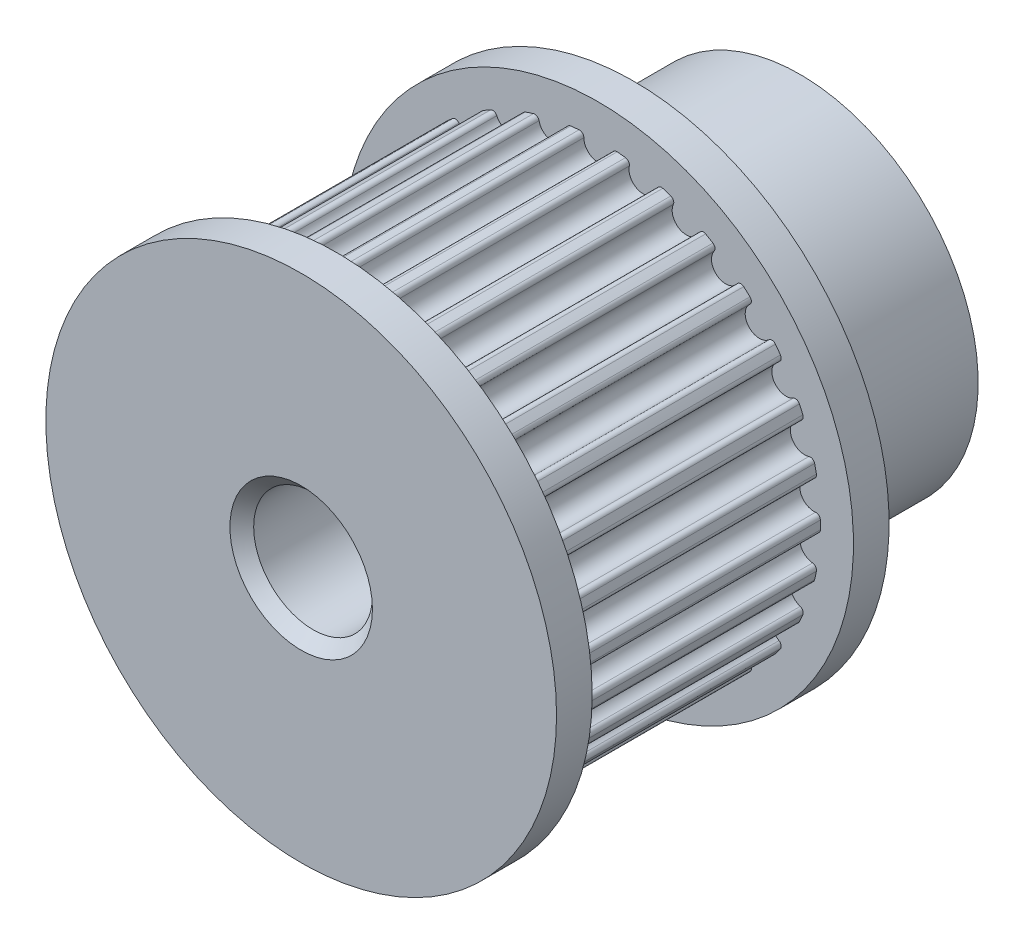
SolidWorks part; units mm, degrees
ref_plane "Front Plane" through (0, 0, 0) normal (0, 0, 1) x (1, 0, 0)
ref_plane "Top Plane" through (0, 0, 0) normal (0, 1, 0) x (1, 0, 0)
ref_plane "Right Plane" through (0, 0, 0) normal (1, 0, 0) x (0, 0, -1)
ref_axis "Axis1" through (0, 0, 55) along (0, 0, -1)
sketch "SketchRevolveGearBelt01" plane through (0, 0, 0) normal (1, 0, 0) x (0, 0, -1)
  line L0 (0, 0) -> (1, 0) construction
  line L1 (5.5, 0) -> (5.5, 9.3588)
  line L2 (5.5, 9.3588) -> (-5.5, 9.3588)
  line L3 (-5.5, 9.3588) -> (-5.5, 0)
  line L4 (-5.5, 0) -> (5.5, 0)
  dimension "GearBeltSide1" = 5.5
  dimension "GearBeltOutsideDiameter" = 9.3588
  dimension "GearBeltSide2" = 5.5
revolve "GearBelt01" add sketch "SketchRevolveGearBelt01" angle 360 about L0
sketch "SketchToothGearBelt01" plane through (0, 0, 0) normal (0, 0, 1) x (1, 0, 0)
  line L0 (-0.8012, 9.3244) -> (0, 11.8988)
  line L1 (0, 11.8988) -> (0.8012, 9.3244)
  arc A0 (0.8012, 9.3244) -> (0.6, 9.1398) centre (0.7853, 9.1398) ccw
  arc A1 (0.6, 9.1398) -> (-0.6, 9.1398) centre (0, 9.1398) cw
  arc A2 (-0.6, 9.1398) -> (-0.8012, 9.3244) centre (-0.7853, 9.1398) ccw
  dimension "GearBeltToothR1" = 0.3706
  dimension "GearBeltToothR2" = 1.2
  dimension "GearBeltToothCapX1" = 0.8012
  dimension "GearBeltToothCapY1" = 2.5744
  dimension "GearBeltToothCapX2" = 0.8012
  dimension "GearBeltToothCapY2" = 2.5744
extrude "ToothExtrudeCutGearBelt01" cut sketch "SketchToothGearBelt01" against normal blind 5.6 and the other way blind 5.6
ref_axis "Axis2" through (10.2947, 0, 0) along (-1, 0, 0)
ref_plane "Plane1" through (0, 0, 0) normal (0, 0, -1) x (1, 0, 0)
pattern_circular "PatternGearBelt01" count 30 every 12 about axis through (0, 0, 55) along (0, 0, -1) of "ToothExtrudeCutGearBelt01"
sketch "Sketch5" plane through (0, 0, 5.5) normal (0, 0, 1) x (1, 0, 0)
  circle A0 centre (0, 0) radius 10.75
extrude "Boss-Extrude1" add sketch "Sketch5" along normal blind 1.5
sketch "Sketch6" plane through (0, 0, -5.5) normal (0, 0, -1) x (-1, 0, 0)
  circle A0 centre (0, 0) radius 10.75
extrude "Boss-Extrude2" add sketch "Sketch6" along normal blind 1.5
sketch "Sketch7" plane through (0, 0, -7) normal (0, 0, -1) x (-1, 0, 0)
  circle A0 centre (0, 0) radius 7.5
extrude "Boss-Extrude3" add sketch "Sketch7" along normal blind 7
sketch "Sketch8" plane through (0, 0, -14) normal (0, 0, -1) x (-1, 0, 0)
  circle A0 centre (0, 0) radius 2.5
  dimension "D1" = 5
extrude "Cut-Extrude2" cut sketch "Sketch8" against normal through all
chamfer "Chamfer1" distance 0.5 angle 45 2 edges at (-2.5, 0, -14) (-2.5, 0, 7)
